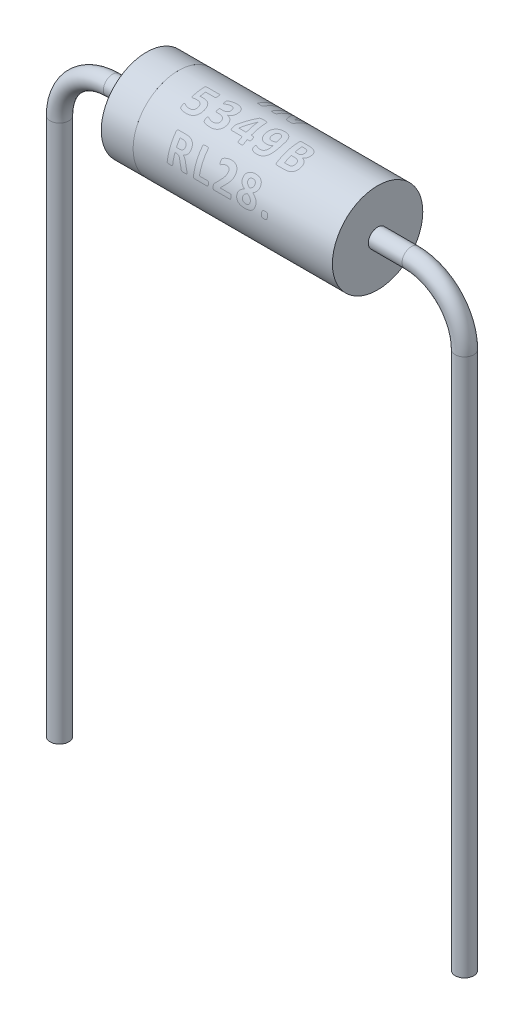
SolidWorks part; units mm, degrees
other "Wire"
other "Cathode Silver Band"
other "Diode"
ref_plane "Front Plane" through (0, 0, 0) normal (0, 0, 1) x (1, 0, 0)
ref_plane "Top Plane" through (0, 0, 0) normal (0, 1, 0) x (1, 0, 0)
ref_plane "Right Plane" through (0, 0, 0) normal (1, 0, 0) x (0, 0, -1)
sketch "Sketch1" plane through (0, 0, 0) normal (1, 0, 0) x (0, 0, -1)
  circle A0 centre (0, 0) radius 1.7
  circle A1 centre (0, 0) radius 0.35
  dimension "D1" = 3.4
  dimension "D2" = 0.7
extrude "Boss-Extrude1" add sketch "Sketch1" along normal mid plane 8.7
sketch "Sketch2" plane through (-4.35, 0, 0) normal (-1, 0, 0) x (0, 0, 1)
  circle A1 centre (0, 0) radius 1.7 construction
  circle A2 centre (0, 0) radius 1.69
  circle A3 centre (0, 0) radius 1.69
  circle A4 centre (0, 0) radius 1.7
  dimension "D1" = 0.01
extrude "Cut-Extrude1" cut sketch "Sketch2" against normal blind 1.2
sketch "Sketch3" plane through (-3.15, 0, 0) normal (-1, 0, 0) x (0, 0, 1)
  circle A0 centre (0, 0) radius 1.69 construction
  circle A1 centre (0, 0) radius 1.69
  circle A2 centre (0, 0) radius 1.7 construction
  circle A3 centre (0, 0) radius 1.7
extrude "Boss-Extrude2" add sketch "Sketch3" along normal up to surface (1.2 mm away) separate body up to face at (-4.35, 0, -0.35)
ref_plane "Plane1" through (0, 5, 0) normal (0, 1, 0) x (1, 0, 0)
sketch "Sketch5" plane through (0, 0, 0) normal (0, 0, 1) x (1, 0, 0)
  line L0 (0, 0) -> (-5.62, 0)
  line L1 (-7.62, -2) -> (-7.62, -22.2384)
  line L2 (0, 0) -> (5.62, 0)
  line L3 (7.62, -2) -> (7.62, -22.2384)
  arc A0 (-5.62, 0) -> (-7.62, -2) centre (-5.62, -2) ccw
  arc A1 (5.62, 0) -> (7.62, -2) centre (5.62, -2) cw
  dimension "D2" = 2
  dimension "D3" = 58
  dimension "D1" = 15.24
sketch "Sketch7" plane through (0, 5, 0) normal (0, 1, 0) x (1, 0, 0)
  line L0 (0, 0) -> (0, 0.5) construction
  line L1 (0, 0.5) -> (0, 2) construction
  line L2 (0, 0) -> (0, -1) construction
  line L3 (0, -1) -> (0, -2.5) construction
  line L4 (-4.35, 2) -> (4.35, 2) construction
  line L5 (-4.35, 0.5) -> (4.35, 0.5) construction
  line L6 (-4.35, -1) -> (4.35, -1) construction
  line L7 (-4.35, -2.5) -> (4.35, -2.5) construction
  line L8 (4.35, -1.7) -> (4.35, 1.7) construction
  line L9 (0, 2) -> (0, 4.4764) construction
  line L10 (-4.35, 4.4764) -> (4.35, 4.4764) construction
  line L11 (0, 4.4764) -> (0, 4.9764) construction
  line L12 (0, 4.9764) -> (0, 6.243) construction
  line L13 (0, 6.243) -> (0, 6.443) construction
  circle A0 centre (0, 4.9764) radius 1.4666 construction
  circle A1 centre (0, 4.9764) radius 1.2666 construction
  text T0 "GA" font "Calibri" height 1
  text T1 "IN" font "Calibri" height 1
  text T2 "5349B" font "Calibri" height 1
  text T3 "RL28." font "Calibri" height 1
  text T4 "ON" font "Calibri" height 1
  dimension "D5" = 0.5
  dimension "D6" = 0.2
  dimension "D1" = 1
  dimension "D2" = 1.5
  dimension "D3" = 1.5
  dimension "D4" = 0.5
wrap "Wrap1" sketch "Sketch7" wrap type scribe source sketch "Sketch7" face at (4.35, 0, -1.7)
sketch "Sketch8" plane through (0, 5, 0) normal (0, 1, 0) x (1, 0, 0)
  circle A0 centre (0, 4.9764) radius 1.4666 construction
  circle A1 centre (0, 4.9764) radius 1.4666
  circle A2 centre (0, 4.9764) radius 1.2666 construction
  circle A3 centre (0, 4.9764) radius 1.2666
wrap "Wrap2" sketch "Sketch8" wrap type scribe source sketch "Sketch8" face at (0.5739, -1.6258, -0.3379)
sketch "Sketch6" plane through (0, 0, 0) normal (1, 0, 0) x (0, 0, -1)
  circle A0 centre (0, 0) radius 0.35
  dimension "D1" = 0.7
sweep "Sweep1" add profiles "Sketch6" path "Sketch5"
